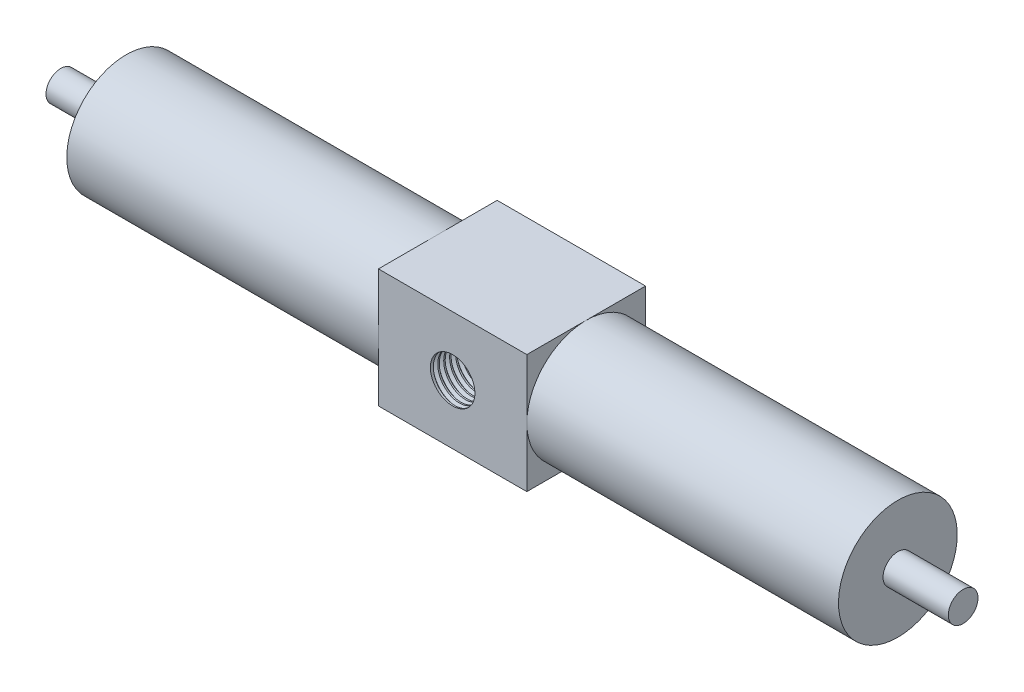
SolidWorks part; units mm, degrees
ref_plane "Front Plane" through (0, 0, 0) normal (0, 0, 1) x (1, 0, 0)
ref_plane "Top Plane" through (0, 0, 0) normal (0, 1, 0) x (1, 0, 0)
ref_plane "Right Plane" through (0, 0, 0) normal (1, 0, 0) x (0, 0, -1)
sketch "Sketch1" plane through (0, 0, 0) normal (0, 0, 1) x (1, 0, 0)
  line L0 (-170.3324, 133.4309) -> (133.6676, 133.4309) construction
  line L1 (-148.3324, 138.4309) -> (-148.3324, 153.4309)
  line L2 (-148.3324, 146.032) -> (-148.3324, -27.5599) construction
  line L3 (-148.3324, 153.4309) -> (111.6676, 153.4309)
  line L4 (111.6676, -27.5599) -> (111.6676, 146.032) construction
  line L5 (111.6676, 153.4309) -> (111.6676, 138.4309)
  line L6 (-148.3324, 138.4309) -> (-170.3324, 138.4309)
  line L7 (-170.3324, 138.4309) -> (-170.3324, 133.4309)
  line L8 (111.6676, 146.032) -> (111.6676, 118.4309) construction
  line L11 (111.6676, 138.4309) -> (133.6676, 138.4309)
  line L12 (133.6676, 138.4309) -> (133.6676, 133.4309)
  line L13 (-170.3324, 133.4309) -> (133.6676, 133.4309)
  dimension "D1" = 5
  dimension "D2" = 22
  dimension "D3" = 40
  dimension "D4" = 22
  dimension "D5" = 90
  dimension "D6" = 5
revolve "Revolve2" add sketch "Sketch1" angle 360 about L0
sketch "Sketch4" plane through (0, 0, 0) normal (0, 0, 1) x (1, 0, 0)
  line L0 (-148.3324, 113.4309) -> (111.6676, 113.4309) construction
  line L1 (-43.3324, 153.4309) -> (6.6676, 153.4309)
  line L2 (-43.3324, 153.4309) -> (-43.3324, 113.4309)
  line L3 (-43.3324, 113.4309) -> (6.6676, 113.4309)
  line L4 (6.6676, 153.4309) -> (6.6676, 113.4309)
  line L5 (-43.3324, 153.4309) -> (6.6676, 113.4309) construction
  line L6 (-43.3324, 113.4309) -> (6.6676, 153.4309) construction
  line L7 (111.6676, 113.4309) -> (111.6676, 153.4309) construction
  point P0 (-18.3324, 133.4309)
  dimension "D1" = 40
  dimension "D2" = 50
  dimension "D3" = 130
extrude "Boss-Extrude2" add sketch "Sketch4" along normal mid plane 40
sketch "Sketch5" plane through (0, 0, 20) normal (0, 0, 1) x (1, 0, 0)
  line L0 (111.6676, 113.4309) -> (111.6676, 153.4309) construction
  circle A0 centre (-18.3324, 133.4309) radius 7.5
  dimension "D1" = 15
  dimension "D2" = 130
extrude "Cut-Extrude2" cut sketch "Sketch5" against normal blind 58
thread "Thread2" pitch 2 method cut profile "Thread Profile2" start angle 180, offset 0, length 40, pitch 2, diameter 15
ref_plane "Plane2" through (-10.8324, 133.4309, 20) normal (0, 1, 0) x (1, 0, 0)
sketch "Thread Profile2" plane through (-10.8324, 133.4309, 20) normal (0, 1, 0) x (1, 0, 0)
  line L0 (0, 0) -> (0, 2) construction
  line L1 (0, 0) -> (1.0825, 0.625)
  line L2 (1.0825, 0.625) -> (1.0825, 0.875)
  line L3 (1.0825, 0.875) -> (0, 1.5)
  line L4 (1.0825, 0.75) -> (0, 0.75) construction
  line L11 (0, 0) -> (0, 1.5)
  point P2 (0, 0)
  dimension "Pitch" = 2
  dimension "Profile_Angle" = 60
  dimension "Profile_Land" = 0.25
  dimension "Profile_Height" = 1.0825
